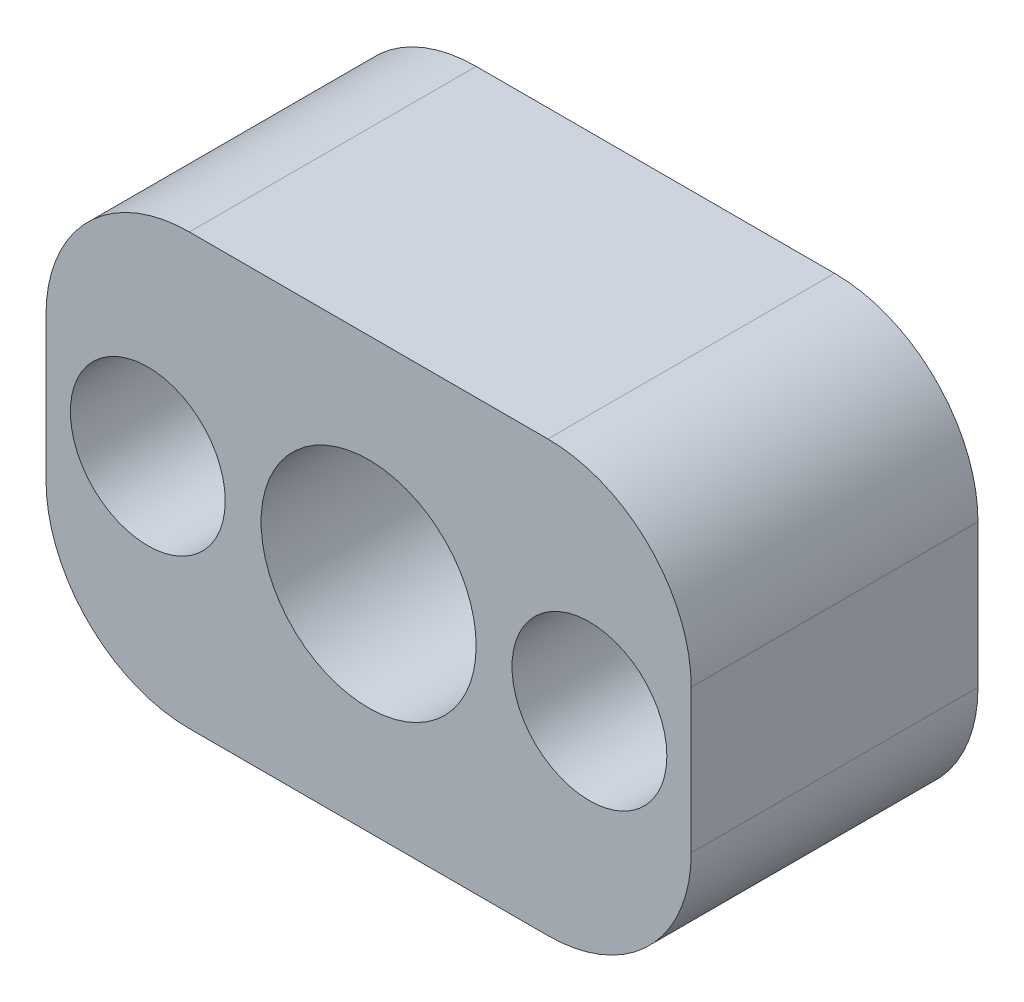
SolidWorks part; units mm, degrees
material "Copper"
ref_plane "Front Plane" through (0, 0, 0) normal (0, 0, 1) x (1, 0, 0)
ref_plane "Top Plane" through (0, 0, 0) normal (0, 1, 0) x (1, 0, 0)
ref_plane "Right Plane" through (0, 0, 0) normal (1, 0, 0) x (0, 0, -1)
sketch "Sketch1" plane through (0, 0, 0) normal (0, 0, 1) x (1, 0, 0)
  line L0 (-14.2875, 0) -> (-14.2875, -19.05)
  line L1 (0, 0) -> (-28.575, 0)
  line L2 (0, 0) -> (0, -19.05)
  line L3 (0, -19.05) -> (-28.575, -19.05)
  line L4 (-28.575, 0) -> (-28.575, -19.05)
  line L5 (-28.575, -9.525) -> (0, -9.525)
  circle A0 centre (-14.2875, -9.525) radius 4.7625
  circle A1 centre (-24.0665, -9.525) radius 1.778
  circle A2 centre (-4.5085, -9.525) radius 1.778
  dimension "D3" = 9.525
  dimension "D4" = 3.556
  dimension "D5" = 3.556
  dimension "D1" = 19.05
  dimension "D2" = 28.575
  dimension "D6" = 9.779
  dimension "D7" = 9.779
extrude "Boss-Extrude1" add sketch "Sketch1" along normal blind 12.7 contours A1 L5 A0 L0 L1 L4 | A1 L5 L4 L3 L0 A0 | A2 L5 A0 L0 L3 L2 | A2 L5 L2 L1 L0 A0 region at (-6.4539, -4.1559, 0) region at (-22.1211, -4.1559, 0) region at (-6.4539, -14.8941, 0) region at (-22.1211, -14.8941, 0)
fillet "Fillet1" radius 6.35 4 edges at (-28.575, 0, 6.35) (-28.575, -19.05, 6.35) (0, -19.05, 6.35) (0, 0, 6.35)
sketch "Sketch2" plane through (0, 0, 12.7) normal (0, 0, 1) x (1, 0, 0)
  circle A0 centre (-24.0665, -9.525) radius 3.429
  circle A1 centre (-4.5085, -9.525) radius 3.429
  dimension "D1" = 6.858
  dimension "D2" = 6.858
extrude "Cut-Extrude1" cut sketch "Sketch2" against normal blind 6.35
